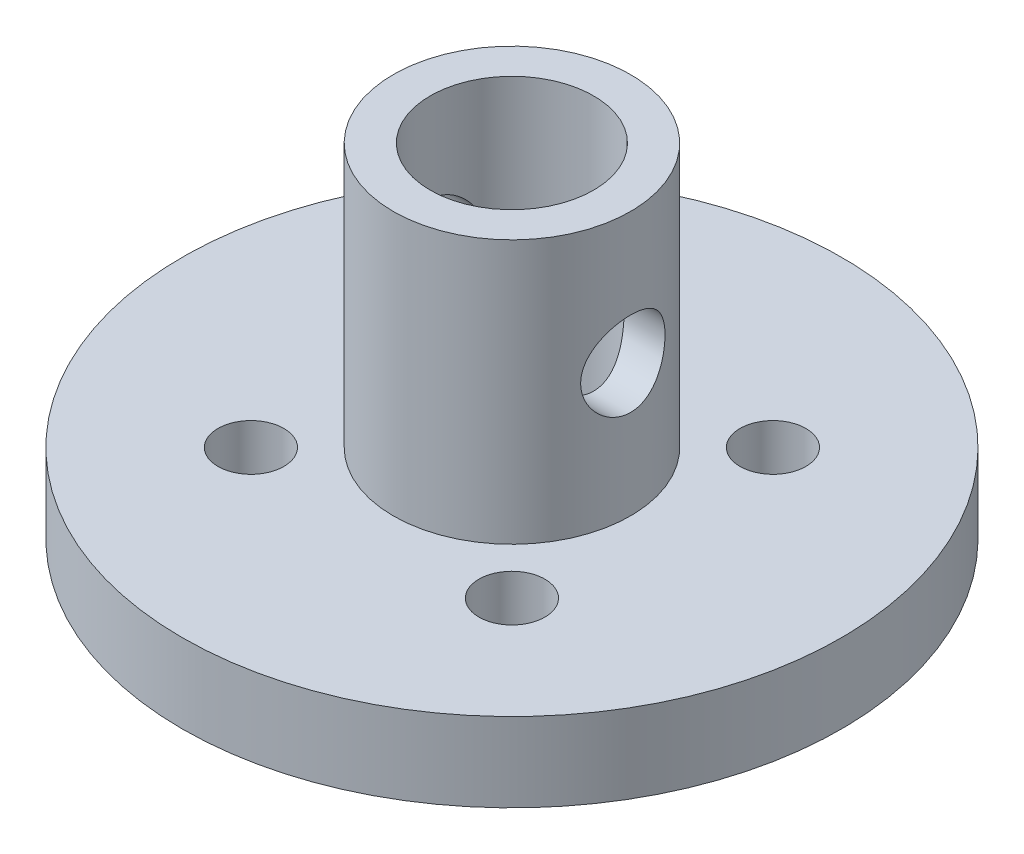
SolidWorks part; units mm, degrees
ref_plane "Alzado" through (0, 0, 0) normal (0, 0, 1) x (1, 0, 0)
ref_plane "Planta" through (0, 0, 0) normal (0, 1, 0) x (1, 0, 0)
ref_plane "Vista lateral" through (0, 0, 0) normal (1, 0, 0) x (0, 0, -1)
sketch "Croquis1" plane through (0, 0, 0) normal (0, 1, 0) x (1, 0, 0)
  line L0 (0, 0) -> (-6.6149, 6.6149) construction
  line L1 (-6.6149, 6.6149) -> (7.3418, -7.3418) construction
  line L2 (0, 0) -> (-6.786, -6.786) construction
  line L3 (-6.786, -6.786) -> (7.1299, 7.1299) construction
  circle A0 centre (0, 0) radius 12.5
  circle A1 centre (-4.9497, 4.9497) radius 1.25
  circle A3 centre (2.3431, -13.6569) radius 1.25
  circle A5 centre (0, 0) radius 3.1
  circle A6 centre (0, 0) radius 4.5
  circle A7 centre (4.9497, 4.9497) radius 1.25
  circle A8 centre (4.9497, -4.9497) radius 1.25
  circle A9 centre (-4.9497, -4.9497) radius 1.25
  point P14 (-1.6569, -4)
  point P23 (0, 0)
  dimension "D1" = 25
  dimension "D2" = 2.5
  dimension "D4" = 7
  dimension "D5" = 6.2
  dimension "D6" = 9
  dimension "D7" = 45
  dimension "D3" = 4
extrude "Saliente-Extruir1" add sketch "Croquis1" along normal blind 3 contours A0 A6 A3 A1 | A6 A5 | A5 region at (-12.1464, 0, 0) region at (0, 0, 0) region at (-4.3727, 0, 0)
extrude "Saliente-Extruir2" add sketch "Croquis1<3>" along normal blind 10 from surface contours A6 | A5 starting at face at (-4.9497, 3, 6.1997)
sketch "Croquis1<3>" plane through (0, 0, 0) normal (0, 1, 0) x (1, 0, 0) same geometry as "Croquis1"
sketch "Croquis2" plane through (0, 0, 0) normal (1, 0, 0) x (0, 0, -1)
  line L0 (3.1, 13) -> (-3.1, 13) construction
  circle A0 centre (0, 8) radius 1.6
  dimension "D1" = 3.2
  dimension "D2" = 5
extrude "Cortar-Extruir1" cut sketch "Croquis2" against normal through all both and the other way through all
